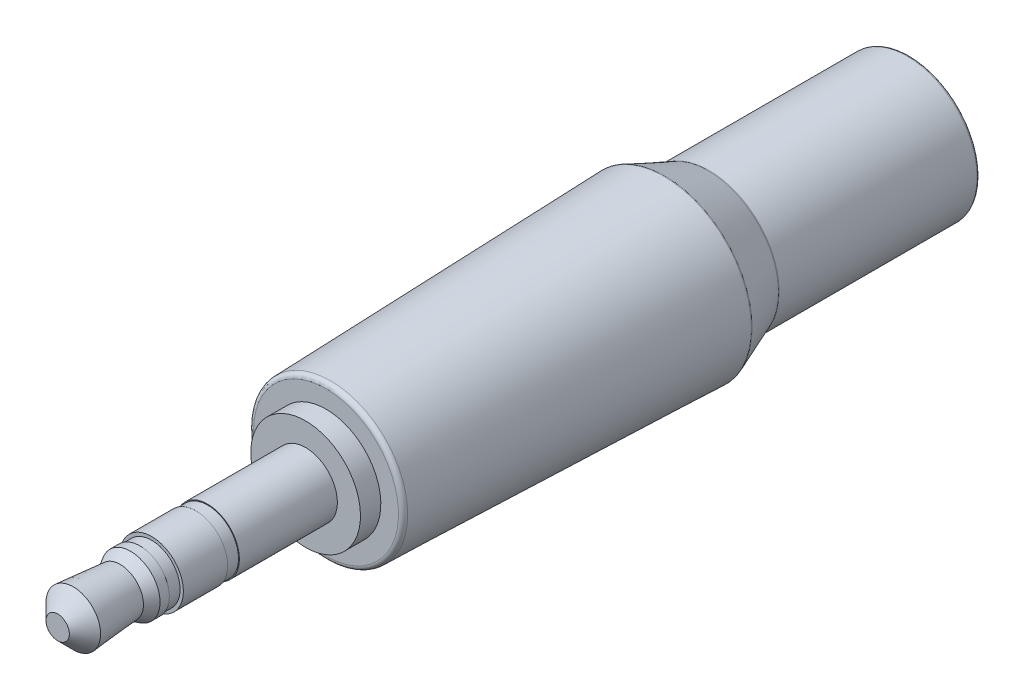
SolidWorks part; units mm, degrees
ref_plane "Front Plane" through (0, 0, 0) normal (0, 0, 1) x (1, 0, 0)
ref_plane "Top Plane" through (0, 0, 0) normal (0, 1, 0) x (1, 0, 0)
ref_plane "Right Plane" through (0, 0, 0) normal (1, 0, 0) x (0, 0, -1)
sketch "Sketch1" plane through (0, 0, 0) normal (1, 0, 0) x (0, 0, -1)
  line L0 (4.479, 1.6002) -> (3.971, 1.6002)
  line L1 (0, 0) -> (14.605, 0)
  line L2 (5.114, 1.7272) -> (7.527, 1.7272)
  line L4 (0, 0) -> (0, 0.635)
  line L5 (0.8509, 1.4859) -> (3.3991, 1.27)
  line L6 (3.3991, 1.27) -> (3.971, 1.6002)
  line L7 (4.479, 1.6002) -> (4.479, 1.5494)
  line L8 (4.479, 1.5494) -> (5.114, 1.5494)
  line L9 (5.114, 1.5494) -> (5.114, 1.7272)
  line L10 (7.527, 1.7272) -> (7.527, 1.6827)
  line L11 (7.527, 1.6827) -> (8.162, 1.6828)
  line L12 (8.162, 1.6828) -> (8.162, 1.7272)
  line L13 (8.162, 1.7272) -> (13.496, 1.7272)
  line L14 (13.496, 1.7272) -> (13.496, 2.9845)
  line L15 (13.496, 2.9845) -> (14.605, 2.9845)
  line L16 (14.605, 2.9845) -> (14.605, 0)
  line L17 (0, 0.635) -> (0.8509, 1.4859)
  dimension "D2" = 14.605
  dimension "D3" = 0.635
  dimension "D4" = 5.334
  dimension "D5" = 0.635
  dimension "D6" = 1.4859
  dimension "D7" = 0.635
  dimension "D8" = 1.6002
  dimension "D9" = 45
  dimension "D10" = 4.843
  dimension "D11" = 1.27
  dimension "D12" = 2.413
  dimension "D13" = 2.9845
  dimension "D14" = 1.7272
  dimension "D15" = 0.508
  dimension "D16" = 30
  dimension "D17" = 1.6827
  dimension "D18" = 1.5494
revolve "Revolve1" add sketch "Sketch1" angle 360 about L1
sketch "Sketch2" plane through (0, 0, 0) normal (1, 0, 0) x (0, 0, -1)
  line L0 (14.605, 0) -> (14.605, 4.191)
  line L1 (14.605, -2.9845) -> (14.605, 2.9845) construction
  line L2 (14.605, 4.191) -> (33.02, 4.7625)
  line L3 (33.02, 4.7625) -> (35.433, 3.81)
  line L4 (35.433, 3.81) -> (46.355, 3.81)
  line L5 (14.605, 0) -> (46.355, 0)
  line L6 (46.355, 0) -> (46.355, 3.81)
  dimension "D1" = 31.75
  dimension "D2" = 4.191
  dimension "D3" = 18.415
  dimension "D4" = 4.7625
  dimension "D5" = 3.81
  dimension "D6" = 10.922
revolve "Revolve2" add sketch "Sketch2" angle 360 about L5
fillet "Fillet1" radius 0.254 1 edges at (4.191, 0, -14.605)
fillet "Fillet2" radius 0.127 1 edges at (4.7625, 0, -33.02)
fillet "Fillet3" radius 0.127 1 edges at (3.81, 0, -35.433)
fillet "Fillet4" radius 0.127 1 edges at (3.81, 0, -46.355)
sketch "Sketch3" plane through (0, 0, -46.355) normal (0, 0, -1) x (-1, 0, 0)
  line L0 (-3.683, 0) -> (3.683, 0) construction
  circle A0 centre (0, 0) radius 3.683 construction
  point P5 (0, 0)
  point P6 (1.4224, 0)
  point P8 (-1.4224, 0)
  dimension "D1" = 1.4224
  dimension "D2" = 1.4224
other "CPoint1" parameters "Diameter"=1.4224, "StubLength"=5.08
ref_axis "Axis1" through (1.4224, 0, -56.355) along (0, 0, 1)
other "CPoint2" parameters "Diameter"=1.4224, "StubLength"=5.08
ref_axis "Axis2" through (0, 0, -56.355) along (0, 0, 1)
other "CPoint3" parameters "Diameter"=1.4224, "StubLength"=5.08
ref_axis "Axis3" through (-1.4224, 0, -56.355) along (0, 0, 1)
